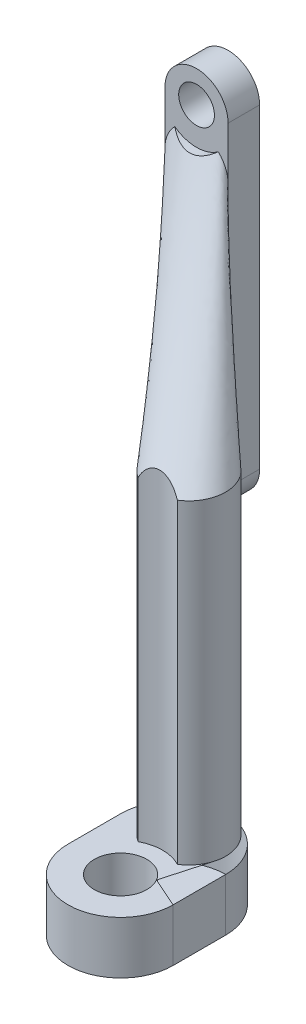
SolidWorks part; units mm, degrees
ref_plane "Ebene vorne" through (0, 0, 0) normal (0, 0, 1) x (1, 0, 0)
ref_plane "Ebene oben" through (0, 0, 0) normal (0, 1, 0) x (1, 0, 0)
ref_plane "Ebene rechts" through (0, 0, 0) normal (1, 0, 0) x (0, 0, -1)
sketch "Skizze1" plane through (0, 0, 0) normal (0, 1, 0) x (1, 0, 0)
  line L0 (0, 0) -> (0, 5) construction
  line L1 (-5, 0) -> (-5, 5)
  line L2 (5, 0) -> (5, 5)
  arc A1 (-5, 0) -> (5, 0) centre (0, 0) ccw
  arc A2 (5, 5) -> (-5, 5) centre (0, 5) ccw
  point P4 (0, 2.5)
  dimension "D2" = 10
  dimension "D3" = 5
extrude "Aufsatz-Linear austragen1" add sketch "Skizze1" along normal blind 5
ref_plane "Ebene1" through (0, 0, -16.1) normal (0, 0, 1) x (1, 0, 0)
sketch "Skizze3" plane through (0, 0, -16.1) normal (0, 0, 1) x (1, 0, 0)
  circle A0 centre (-8.87, 50.91) radius 3
  point P0 (-8.87, 50.91)
  dimension "D2" = 6
  dimension "D1" = 8.87
  dimension "D4" = 50.91
sketch "Skizze4" plane through (0, 5, 0) normal (0, 1, 0) x (1, 0, 0)
  circle A0 centre (0, 0) radius 2.5
  dimension "D1" = 5
extrude "Schnitt-Linear austragen1" cut sketch "Skizze4" against normal blind 10
sketch "Skizze5" plane through (0, 5, 0) normal (0, 1, 0) x (1, 0, 0)
  line L0 (0, 0) -> (0, 6.5) construction
  circle A0 centre (0, 6.5) radius 3.5
  arc A1 (5, 5) -> (-5, 5) centre (0, 5) ccw construction
  dimension "D1" = 7
extrude "Aufsatz-Linear austragen2" add sketch "Skizze5" along normal blind 30
sketch "Skizze6" plane through (0, 35, 0) normal (0, 1, 0) x (1, 0, 0)
  circle A0 centre (0, 6.5) radius 3.5
loft "Ausformung4" add profiles "Skizze6", "Skizze3" connector at (0, 35, -3) connector at (-11.8686, 51.0029, -16.1)
sketch "Skizze7" plane through (0, 5, 0) normal (0, 1, 0) x (1, 0, 0)
  circle A0 centre (0, 0) radius 4
  dimension "D1" = 8
extrude "Schnitt-Linear austragen2" cut sketch "Skizze7" along normal blind 40
sketch "Skizze8" plane through (0, 0, -16.1) normal (0, 0, 1) x (1, 0, 0)
  line L0 (-8.87, 55.91) -> (-8.87, 25.91) construction
  line L1 (-5.87, 55.91) -> (-5.87, 25.91)
  line L2 (-11.87, 55.91) -> (-11.87, 25.91)
  line L3 (-8.87, 53.91) -> (-8.87, 47.91) construction
  arc A0 (-5.87, 55.91) -> (-11.87, 55.91) centre (-8.87, 55.91) ccw
  arc A1 (-11.87, 25.91) -> (-5.87, 25.91) centre (-8.87, 25.91) ccw
  circle A2 centre (-8.87, 50.91) radius 3 construction
  circle A4 centre (-8.87, 55.91) radius 1.7
  circle A5 centre (-8.87, 25.91) radius 1.7
  point P2 (-8.87, 40.91)
  point P8 (0, 0)
  point P9 (-8.87, 50.91)
  dimension "D4" = 3.4
  dimension "D5" = 3.4
  dimension "D1" = 5
  dimension "D2" = 6
  dimension "D3" = 25
extrude "Aufsatz-Linear austragen3" add sketch "Skizze8" against normal blind 3
sketch "Skizze10" plane through (0, 0, -16.1) normal (0, 0, 1) x (1, 0, 0)
  circle A0 centre (-8.87, 55.91) radius 3.5
  dimension "D1" = 7
extrude "Schnitt-Linear austragen3" cut sketch "Skizze10" along normal blind 10
